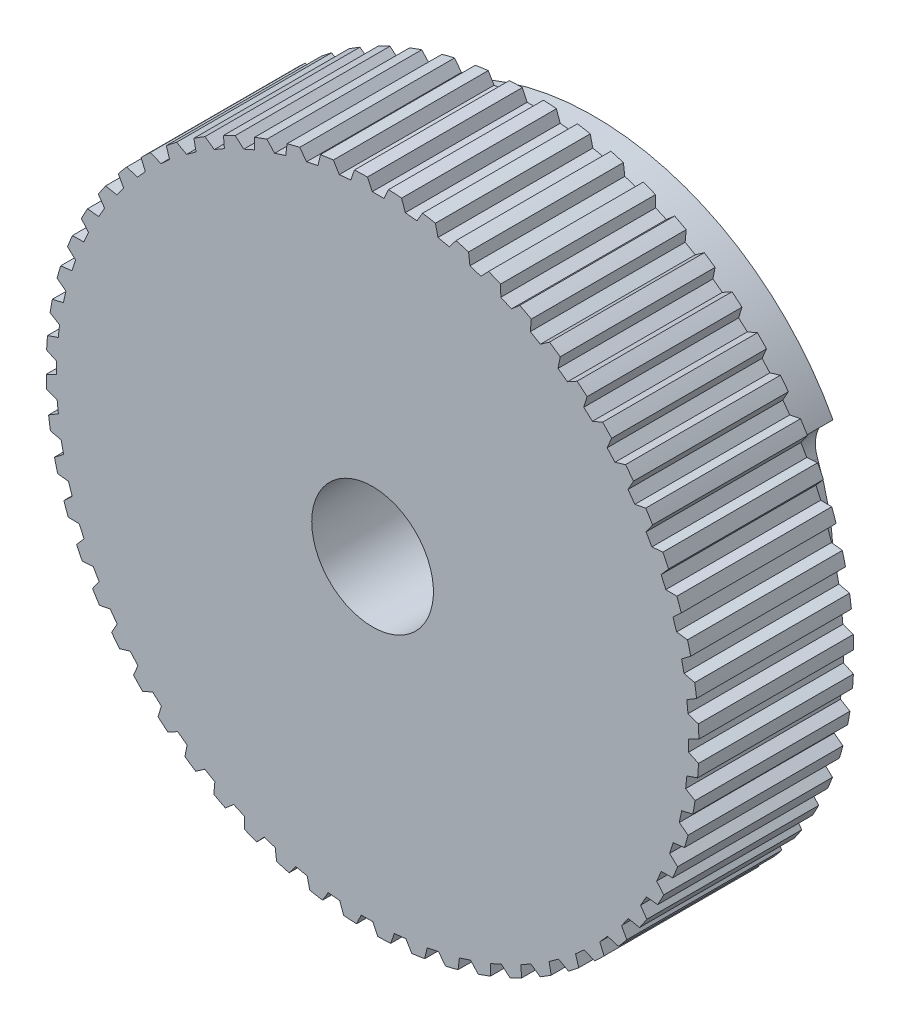
SolidWorks part; units mm, degrees
ref_plane "Plan de face" through (0, 0, 0) normal (0, 0, 1) x (1, 0, 0)
ref_plane "Plan de dessus" through (0, 0, 0) normal (0, 1, 0) x (1, 0, 0)
ref_plane "Plan de droite" through (0, 0, 0) normal (1, 0, 0) x (0, 0, -1)
sketch "Esquisse1" plane through (0, 0, 0) normal (0, 0, 1) x (1, 0, 0)
  circle A0 centre (0, 0) radius 29.5
  dimension "D1" = 59
extrude "Extrusion3" add sketch "Esquisse1" along normal blind 14
sketch "Esquisse7" plane through (0, 0, 0) normal (0, 0, -1) x (-1, 0, 0)
  circle A0 centre (0, 0) radius 24.5
extrude "Extrusion4" add sketch "Esquisse7" along normal blind 6
sketch "Esquisse8" plane through (0, 0, -6) normal (0, 0, -1) x (-1, 0, 0)
  line L0 (-19.0581, 10.3342) -> (-21.6204, 11.5242)
  line L1 (10.926, -18.7251) -> (12.558, -21.0368)
  arc A0 (-21.6204, 11.5242) -> (12.558, -21.0368) centre (0, 0) ccw
  circle A1 centre (0, 0) radius 24.5 construction
  arc A2 (10.926, -18.7251) -> (-19.0581, 10.3342) centre (0, 0) cw
extrude "Extrusion5" cut sketch "Esquisse8" against normal blind 6
fillet "Congé1" radius 3 1 edges at (19.0581, 10.3342, -3)
fillet "Congé2" radius 3 1 edges at (-10.926, -18.7251, -3)
sketch "Esquisse9" plane through (0, 0, -6) normal (0, 0, -1) x (-1, 0, 0)
  circle A0 centre (0, 0) radius 5.5
extrude "Extrusion6" cut sketch "Esquisse9" against normal through all
sketch "Esquisse10" plane through (0, 0, 0) normal (0, 0, -1) x (-1, 0, 0)
  line L0 (1.5, -29.5771) -> (-0.5, -29.5771)
  line L1 (-0.5, -29.5771) -> (-0.0274, -28.5637)
  line L2 (-0.0274, -28.5637) -> (1.0274, -28.5637)
  line L3 (1.0274, -28.5637) -> (1.5, -29.5771)
  line L4 (0, 0) -> (0, -40.6353) construction
  dimension "D1" = 50
  dimension "D2" = 25
  dimension "D3" = 2
  dimension "D4" = 1.5
extrude "Extrusion7" cut sketch "Esquisse10" against normal through all
pattern_circular "Répétition circulaire1" count 60 every 6 about axis through (0, 0, 14) along (0, 0, -1) of "Extrusion7"
